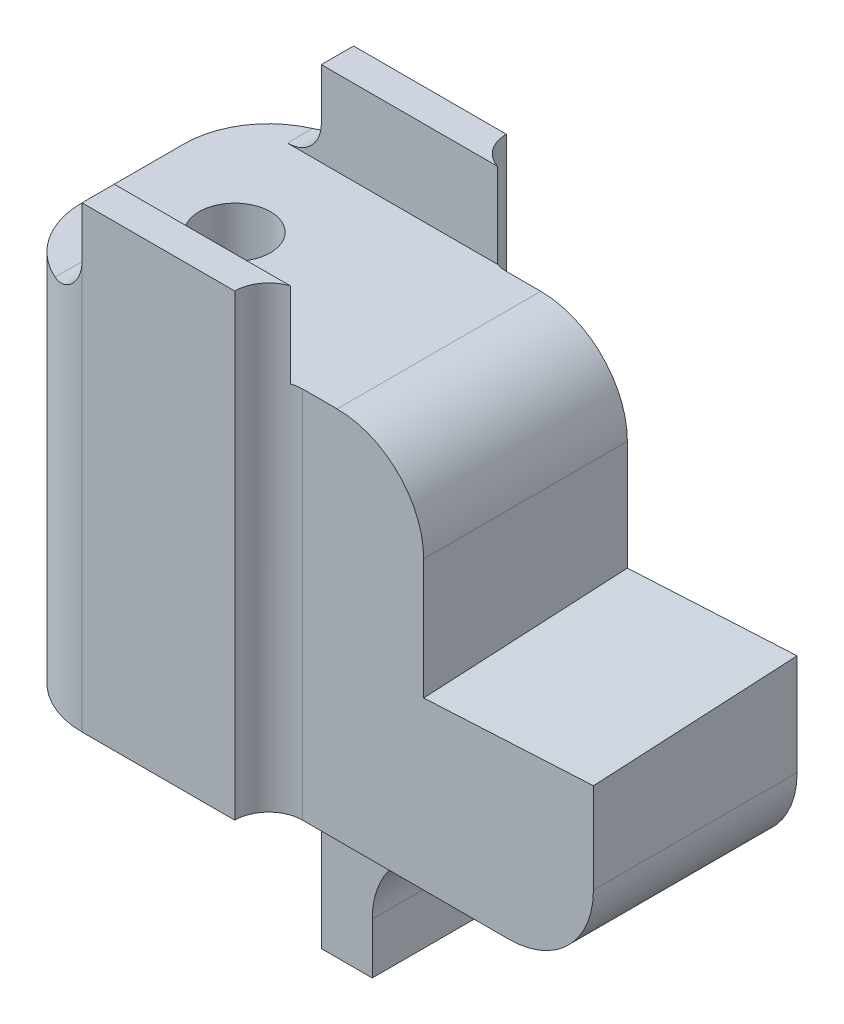
SolidWorks part; units mm, degrees
ref_plane "Front Plane" through (0, 0, 0) normal (0, 0, 1) x (1, 0, 0)
ref_plane "Top Plane" through (0, 0, 0) normal (0, 1, 0) x (1, 0, 0)
ref_plane "Right Plane" through (0, 0, 0) normal (1, 0, 0) x (0, 0, -1)
sketch "Sketch1" plane through (0, 0, 0) normal (0, 1, 0) x (1, 0, 0)
  line L5 (-6, 8) -> (6, 8)
  line L6 (-6, 8) -> (-6, -8)
  line L7 (-6, -8) -> (6, -8)
  line L8 (6, 8) -> (6, -8)
  line L9 (-6, 8) -> (6, -8) construction
  line L10 (-6, -8) -> (6, 8) construction
  line L11 (6, 8) -> (8, 8)
  line L12 (6, 8) -> (6, -8)
  line L13 (6, -8) -> (8, -8)
  line L14 (8, 8) -> (8, -8)
  circle A0 centre (0, 0) radius 2.1
  point P0 (0, 0)
  dimension "D1" = 4.2
  dimension "D2" = 16
  dimension "D3" = 6
  dimension "D4" = 2
extrude "Boss-Extrude1" add sketch "Sketch1" along normal blind 22 contours L8 L5 L6 L7 A0 | L14 L11 L8 L13 region at (0, 0, -7.8) region at (7, 0, 0)
fillet "Fillet1" radius 5 2 edges at (-6, 11, -8) (-6, 11, 8)
sketch "Sketch2" plane through (0, 22, 0) normal (0, 1, 0) x (1, 0, 0)
  line L0 (8, 0) -> (-6, 0) construction
  line L1 (8, 8) -> (-1, 8)
  line L2 (8, 8) -> (8, 6.1)
  line L3 (8, 6.1) -> (-1, 6.1)
  line L4 (-1, 8) -> (-1, 6.1)
  line L5 (8, 8) -> (8, -8) construction
  line L6 (-6, 3) -> (-6, -3) construction
  line L7 (-1, -8) -> (-1, -6.1)
  line L8 (8, -6.1) -> (-1, -6.1)
  line L9 (8, -8) -> (8, -6.1)
  line L10 (8, -8) -> (-1, -8)
  dimension "D1" = 1.9
extrude "Boss-Extrude2" add sketch "Sketch2" along normal blind 5
sketch "Sketch4" plane through (8, 0, 0) normal (1, 0, 0) x (0, 0, -1)
  line L0 (8, 27) -> (8, 0) construction
  line L1 (-6, 0) -> (6, 0)
  line L2 (-6, 0) -> (-6, 22)
  line L3 (-6, 22) -> (6, 22)
  line L4 (6, 0) -> (6, 22)
  line L6 (6.1, 22) -> (-6.1, 22) construction
  point P6 (0, 0)
  dimension "D1" = 2
extrude "Boss-Extrude3" add sketch "Sketch4" along normal offset from surface (9.13 mm away) 23.13 up to face at (-6, 11, 0)
fillet "Fillet2" radius 5.1 1 edges at (17.13, 22, 0)
sketch "Sketch5" plane through (0, 0, 0) normal (0, -1, 0) x (1, 0, 0)
  line L1 (9.1, 4) -> (12.1, 4)
  line L2 (9.1, 4) -> (9.1, -4)
  line L3 (9.1, -4) -> (12.1, -4)
  line L4 (12.1, 4) -> (12.1, -4)
  line L5 (9.1, 4) -> (12.1, -4) construction
  line L6 (9.1, -4) -> (12.1, 4) construction
  circle A0 centre (0, 0) radius 2.1 construction
  point P0 (10.6, 0)
  point P7 (0, 0)
  dimension "D1" = 9.1
  dimension "D2" = 8
  dimension "D3" = 3
extrude "Boss-Extrude4" add sketch "Sketch5" along normal blind 8
fillet "Fillet3" radius 2 2 edges at (10.6, 0, -4) (10.6, 0, 4)
sketch "Sketch6" plane through (17.13, 0, 0) normal (1, 0, 0) x (0, 0, -1)
  line L0 (-6, 9.8) -> (6, 10.4289)
  line L1 (-6, 16.9) -> (-6, 0) construction
  line L2 (6, 0) -> (6, 16.9) construction
  line L3 (-6, 9.8) -> (-6, 0)
  line L4 (-6, 0) -> (6, 0)
  line L5 (6, 0) -> (6, 10.4289)
  line L6 (6, 0) -> (6, 22) construction
  line L7 (-6, 9.8) -> (6, 9.8) construction
  dimension "D1" = 9.8
  dimension "D2" = 3
extrude "Boss-Extrude5" add sketch "Sketch6" along normal blind 10
sketch "Sketch8" plane through (0, 0, 6) normal (0, 0, 1) x (1, 0, 0)
  line L0 (17.13, 9.8) -> (27.13, 10.3241)
  line L1 (27.13, 10.3241) -> (27.13, 9.8)
  line L2 (27.13, 9.8) -> (17.13, 9.8) construction
  line L3 (17.13, 9.8) -> (27.13, 9.8)
  dimension "D1" = 3
extrude "Boss-Extrude6" add sketch "Sketch8" along direction (0, -0.0523, 0.9986) on the side against the normal up to surface (12 mm away) up to face at (15.4229, 9.2016, -6)
fillet "Fillet4" radius 5 1 edges at (12.1, 0, 0)
fillet "Fillet5" radius 2 4 edges at (-1, 22, -7.05) (-1, 22, 7.05) (8, 11, -6) (8, 11, 6)
fillet "Fillet6" radius 5 1 edges at (27.13, 0, 0)
